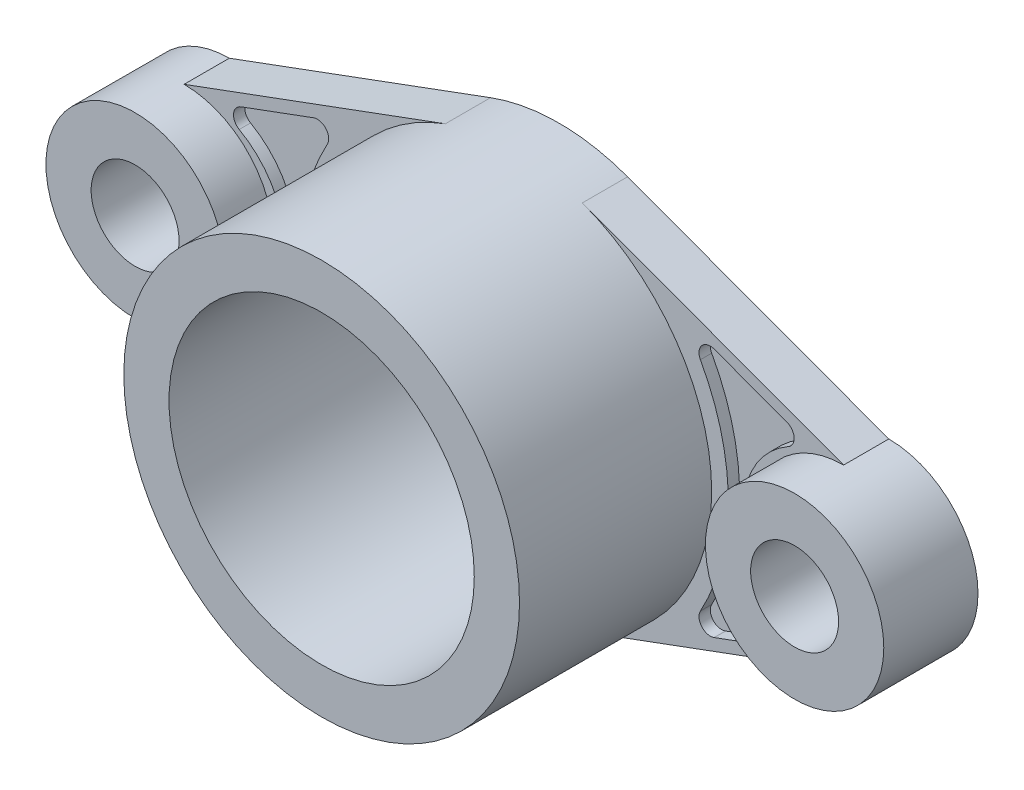
SolidWorks part; units mm, degrees
material "PE High Density"
ref_plane "Front Plane" through (0, 0, 0) normal (0, 0, 1) x (1, 0, 0)
ref_plane "Top Plane" through (0, 0, 0) normal (0, 1, 0) x (1, 0, 0)
ref_plane "Right Plane" through (0, 0, 0) normal (1, 0, 0) x (0, 0, -1)
sketch "Shaft Mount Sketch" plane through (0, 0, 0) normal (0, 0, 1) x (1, 0, 0)
  line L0 (-159.8159, 0) -> (159.8159, 0) construction
  line L1 (0, 87.37) -> (0, -87.37) construction
  line L2 (-87.5, 41.1863) -> (-87.5, -132.4671) construction
  line L3 (-87.5, 23.665) -> (-18.1795, 49.252)
  line L4 (-18.1795, -49.252) -> (-87.5, -23.665)
  line L5 (18.1795, -49.252) -> (87.5, -23.665)
  line L6 (87.5, 23.665) -> (18.1795, 49.252)
  line L7 (-72.4246, 26.0316) -> (-53.1674, 33.1397)
  line L8 (-72.4246, -26.0316) -> (-53.1674, -33.1397)
  line L9 (-52.5, 94.7511) -> (-52.5, -94.7511) construction
  line L10 (72.4246, -26.0316) -> (53.1674, -33.1397)
  line L11 (72.4246, 26.0316) -> (53.1674, 33.1397)
  circle A0 centre (0, 0) radius 52.5
  circle A1 centre (0, 0) radius 40.5
  circle A2 centre (-87.5, 0) radius 23.665
  circle A3 centre (-87.5, 0) radius 11.665
  circle A4 centre (87.5, 0) radius 23.665
  circle A5 centre (87.5, 0) radius 11.665
  arc A6 (-72.8613, 20.6051) -> (-72.8613, -20.6051) centre (-84.5, 0) cw
  arc A7 (-49.5, 28.8794) -> (-49.5, -28.8794) centre (3, 0) ccw
  arc A8 (-53.1674, -33.1397) -> (-49.5, -28.8794) centre (-52.1286, -30.3253) ccw
  arc A9 (-72.4246, -26.0316) -> (-72.8613, -20.6051) centre (-71.3858, -23.2172) cw
  arc A10 (-72.8613, 20.6051) -> (-72.4246, 26.0316) centre (-71.3858, 23.2172) cw
  arc A11 (-49.5, 28.8794) -> (-53.1674, 33.1397) centre (-52.1286, 30.3253) ccw
  arc A12 (72.4246, -26.0316) -> (72.8613, -20.6051) centre (71.3858, -23.2172) ccw
  arc A13 (72.8613, 20.6051) -> (72.8613, -20.6051) centre (84.5, 0) ccw
  arc A14 (72.8613, 20.6051) -> (72.4246, 26.0316) centre (71.3858, 23.2172) ccw
  arc A15 (49.5, 28.8794) -> (53.1674, 33.1397) centre (52.1286, 30.3253) cw
  arc A16 (49.5, 28.8794) -> (49.5, -28.8794) centre (-3, 0) cw
  arc A17 (53.1674, -33.1397) -> (49.5, -28.8794) centre (52.1286, -30.3253) cw
  point P6 (0, 0)
  point P12 (0, 0)
  point P21 (-52.5, 0)
  point P39 (-60.835, 0)
  dimension "D1" = 12
  dimension "D2" = 105
  dimension "D3" = 12
  dimension "D4" = 23.33
  dimension "D6" = 3
  dimension "D8" = 3
  dimension "D9" = 3
  dimension "D10" = 3
  dimension "D5" = 175
  dimension "D7" = 3
extrude "Cylindrical Bore Extrude" add sketch "Shaft Mount Sketch" along normal blind 63 contours A0 A1 region at (0, 51.0151, 0)
extrude "Bolt Holes Extrude" add sketch "Sketch1<3>" along normal blind 25 separate body contours A2 A3 | A4 A5 region at (-71.2396, 16.2604, 0) region at (103.7604, 16.2604, 0)
sketch "Sketch1<3>" plane through (0, 0, 0) normal (0, 0, 1) x (1, 0, 0) same geometry as "Shaft Mount Sketch"
extrude "Shaft Mount Gussets" add sketch "Sketch1<4>" along normal blind 12 contours A2 L4 A0 L3 | L5 A4 L6 A0 | A8 A7 A11 L7 A10 A6 A9 L8 | L10 A17 A16 A15 L11 A14 A13 A12 region at (-55.1277, 0, 0) region at (55.1277, 0, 0)
sketch "Sketch1<4>" plane through (0, 0, 0) normal (0, 0, 1) x (1, 0, 0) same geometry as "Shaft Mount Sketch"
extrude "Flange Extruded Cut 1" cut sketch "Socket Sketch<6>" against normal blind 3 from surface contours A17 L10 A12 A13 A14 L11 A15 A16 region at (60.5948, 0, 0) starting at face at (-55.5036, 0, 12)
sketch "Socket Sketch<6>" plane through (0, 0, 0) normal (0, 0, 1) x (1, 0, 0) same geometry as "Shaft Mount Sketch"
extrude "Flange Extruded Cut 2" cut sketch "Socket Sketch<7>" against normal blind 3 from surface contours A7 A11 L7 A10 A6 A9 L8 A8 region at (-60.5948, 0, 0) starting at face at (-55.5036, 0, 12)
sketch "Socket Sketch<7>" plane through (0, 0, 0) normal (0, 0, 1) x (1, 0, 0) same geometry as "Shaft Mount Sketch"
